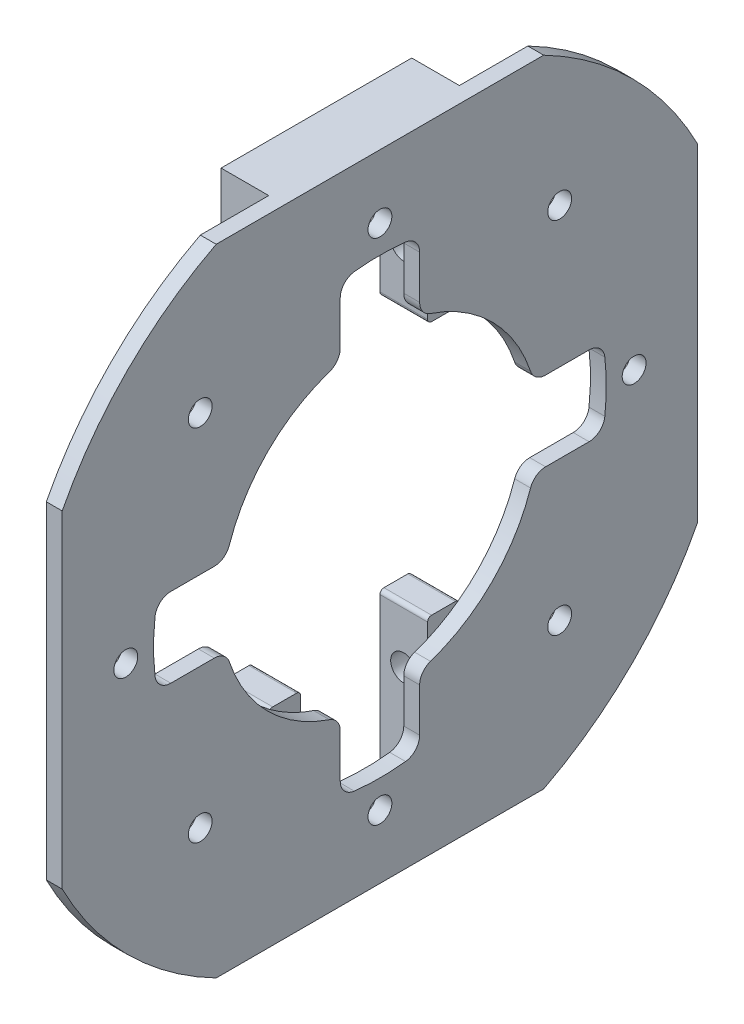
SolidWorks part; units mm, degrees
ref_plane "前视基准面" through (0, 0, 0) normal (0, 0, 1) x (1, 0, 0)
ref_plane "上视基准面" through (0, 0, 0) normal (0, 1, 0) x (1, 0, 0)
ref_plane "右视基准面" through (0, 0, 0) normal (1, 0, 0) x (0, 0, -1)
other "Configuration Table"
ref_plane "基准面1" through (62, 0, 0) normal (1, 0, 0) x (0, 0, -1)
sketch "草图1" plane through (62, 0, 0) normal (1, 0, 0) x (0, 0, -1)
  line L0 (20.6155, 40) -> (-20.6155, 40)
  line L1 (-40, 20.6155) -> (-40, -20.6155)
  line L2 (-20.6155, -40) -> (20.6155, -40)
  line L3 (40, -20.6155) -> (40, 20.6155)
  arc A0 (-20.6155, 40) -> (-40, 20.6155) centre (0, 0) ccw
  arc A1 (-40, -20.6155) -> (-20.6155, -40) centre (0, 0) ccw
  arc A2 (20.6155, -40) -> (40, -20.6155) centre (0, 0) ccw
  arc A3 (40, 20.6155) -> (20.6155, 40) centre (0, 0) ccw
extrude "凸台-拉伸1" add sketch "草图1" against normal blind 2
sketch "草图2" plane through (60, 0, 0) normal (-1, 0, 0) x (0, 0, 1)
  line L0 (5, -28.058) -> (5, -19.3649)
  line L1 (19.3649, -5) -> (28.058, -5)
  line L2 (28.058, 5) -> (19.3649, 5)
  line L3 (5, 19.3649) -> (5, 28.058)
  line L4 (-5, 28.058) -> (-5, 19.3649)
  line L5 (-19.3649, 5) -> (-28.058, 5)
  line L6 (-28.058, -5) -> (-19.3649, -5)
  line L7 (-5, -19.3649) -> (-5, -28.058)
  arc A0 (-5, -28.058) -> (5, -28.058) centre (0, 0) ccw
  arc A1 (5, -19.3649) -> (19.3649, -5) centre (0, 0) ccw
  arc A2 (28.058, -5) -> (28.058, 5) centre (0, 0) ccw
  arc A3 (19.3649, 5) -> (5, 19.3649) centre (0, 0) ccw
  arc A4 (5, 28.058) -> (-5, 28.058) centre (0, 0) ccw
  arc A5 (-5, 19.3649) -> (-19.3649, 5) centre (0, 0) ccw
  arc A6 (-28.058, 5) -> (-28.058, -5) centre (0, 0) ccw
  arc A7 (-19.3649, -5) -> (-5, -19.3649) centre (0, 0) ccw
extrude "切除-拉伸1" cut sketch "草图2" against normal through all
sketch "草图3" plane through (60, 0, 0) normal (-1, 0, 0) x (0, 0, 1)
  line L0 (12, -16) -> (12, -40)
  line L1 (12, -40) -> (-12, -40)
  line L2 (-12, -40) -> (-12, -16)
  line L3 (-12, -16) -> (-8, -16)
  line L4 (-8, -16) -> (-8, -38)
  line L5 (-8, -38) -> (8, -38)
  line L6 (8, -38) -> (8, -16)
  line L7 (8, -16) -> (12, -16)
extrude "凸台-拉伸2" add sketch "草图3" along normal blind 6
sketch "草图4" plane through (60, 0, 0) normal (-1, 0, 0) x (0, 0, 1)
  line L0 (12, 16) -> (8, 16)
  line L1 (8, 16) -> (8, 38)
  line L2 (8, 38) -> (-8, 38)
  line L3 (-8, 38) -> (-8, 16)
  line L4 (-8, 16) -> (-12, 16)
  line L5 (-12, 16) -> (-12, 40)
  line L6 (-12, 40) -> (12, 40)
  line L7 (12, 40) -> (12, 16)
extrude "凸台-拉伸3" add sketch "草图4" along normal blind 6
hole_wizard "Ø3.3 (3.3) 直径孔1" positions "草图6" profile "草图5" hole size "Ø3.3" standard "ANSI Metric"
sketch "草图6" plane through (0, 0, 8) normal (0, 0, -1) x (-1, 0, 0)
  point P0 (-57, -23)
  point P1 (-57, 23)
sketch "草图5" plane through (57, -23, 8) normal (1, 0, 0) x (0, 1, 0)
  line L0 (0, 0) -> (0, 32)
  line L1 (0, 32) -> (1.65, 32)
  line L2 (1.65, 32) -> (1.65, 0)
  line L5 (1.65, 0) -> (0, 0)
  line L11 (0, -6.35) -> (0, 107.95) construction
  dimension "通孔孔直径" = 3.3
  dimension "通孔孔深度" = 32
hole_wizard "Ø3.3 (3.3) 直径孔2" positions "草图8" profile "草图7" hole size "Ø3.3" standard "ANSI Metric"
sketch "草图8" plane through (0, 0, -12) normal (0, 0, -1) x (-1, 0, 0)
  point P0 (-57, -23)
  point P1 (-57, 23)
sketch "草图7" plane through (57, -23, -12) normal (1, 0, 0) x (0, 1, 0)
  line L0 (0, 0) -> (0, 52)
  line L1 (0, 52) -> (1.65, 52)
  line L2 (1.65, 52) -> (1.65, 0)
  line L5 (1.65, 0) -> (0, 0)
  line L11 (0, -6.35) -> (0, 107.95) construction
  dimension "通孔孔直径" = 3.3
  dimension "通孔孔深度" = 52
hole_wizard "Ø3.0 (3) 直径孔1" positions "草图10" profile "草图9" hole size "Ø3.0" standard "ANSI Metric"
sketch "草图10" plane through (62, 0, 0) normal (1, 0, 0) x (0, 0, -1)
  point P0 (0, 32)
  point P1 (-22.6274, 22.6274)
  point P2 (-32, 0)
  point P3 (-22.6274, -22.6274)
  point P4 (0, -32)
  point P5 (22.6274, -22.6274)
  point P6 (32, 0)
  point P7 (22.6274, 22.6274)
sketch "草图9" plane through (62, 32, 0) normal (0, 1, 0) x (0, 0, -1)
  line L0 (0, 0) -> (0, 8)
  line L1 (0, 8) -> (1.5, 8)
  line L2 (1.5, 8) -> (1.5, 0)
  line L5 (1.5, 0) -> (0, 0)
  line L11 (0, -6.35) -> (0, 107.95) construction
  dimension "通孔孔直径" = 3
  dimension "通孔孔深度" = 8
fillet "圆角1" radius 0.5 12 edges at (57, -38, 8) (57, -16, 8) (57, 16, -8) (57, 38, 8) (57, -16, 12) (57, 38, -8) (57, 16, 8) (57, 16, 12) (57, -16, -8) (57, -38, -8) (57, 16, -12) (57, -16, -12) tangent propagation no
fillet "圆角2" radius 2 16 edges at (61, -5, -19.3649) (61, 5, 19.3649) (61, 5, -19.3649) (61, 5, -28.058) (61, -19.3649, 5) (61, 28.058, 5) (61, 19.3649, 5) (61, 5, 28.058) (61, 19.3649, -5) (61, -5, 28.058) (61, -5, 19.3649) (61, -28.058, 5) (61, -19.3649, -5) (61, -28.058, -5) (61, -5, -28.058) (61, 28.058, -5) tangent propagation no
